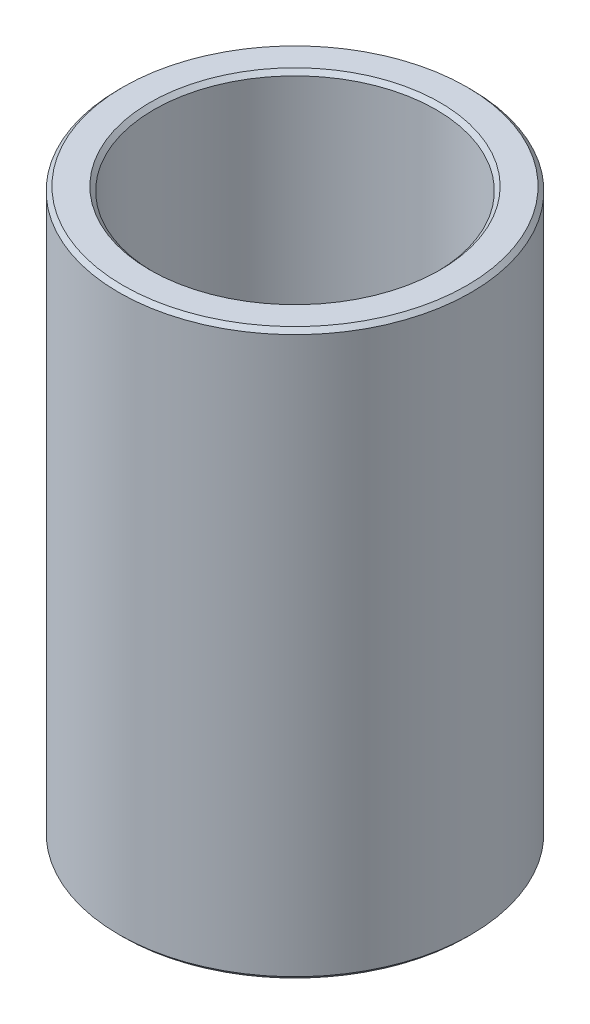
SolidWorks part; units mm, degrees
ref_plane "Front Plane" through (0, 0, 0) normal (0, 0, 1) x (1, 0, 0)
ref_plane "Top Plane" through (0, 0, 0) normal (0, 1, 0) x (1, 0, 0)
ref_plane "Right Plane" through (0, 0, 0) normal (1, 0, 0) x (0, 0, -1)
sketch "Sketch1" plane through (0, 0, 0) normal (0, 1, 0) x (1, 0, 0)
  circle A0 centre (0, 0) radius 32.5
  dimension "SLEEVE_OD" = 65
extrude "Boss-Extrude1" add sketch "Sketch1" along normal blind 104.1881
sketch "Sketch2" plane through (0, 0, 0) normal (0, 1, 0) x (1, 0, 0)
  circle A0 centre (0, 0) radius 26.0366
  dimension "BORE_D" = 52.0733
extrude "Cut-Extrude1" cut sketch "Sketch2" along normal through all
chamfer "Chamfer1" distance 0.7553 angle 45 4 edges at (0, 104.1881, 26.0366) (0, 0, 26.0366) (0, 0, 32.5) (0, 104.1881, 32.5)
